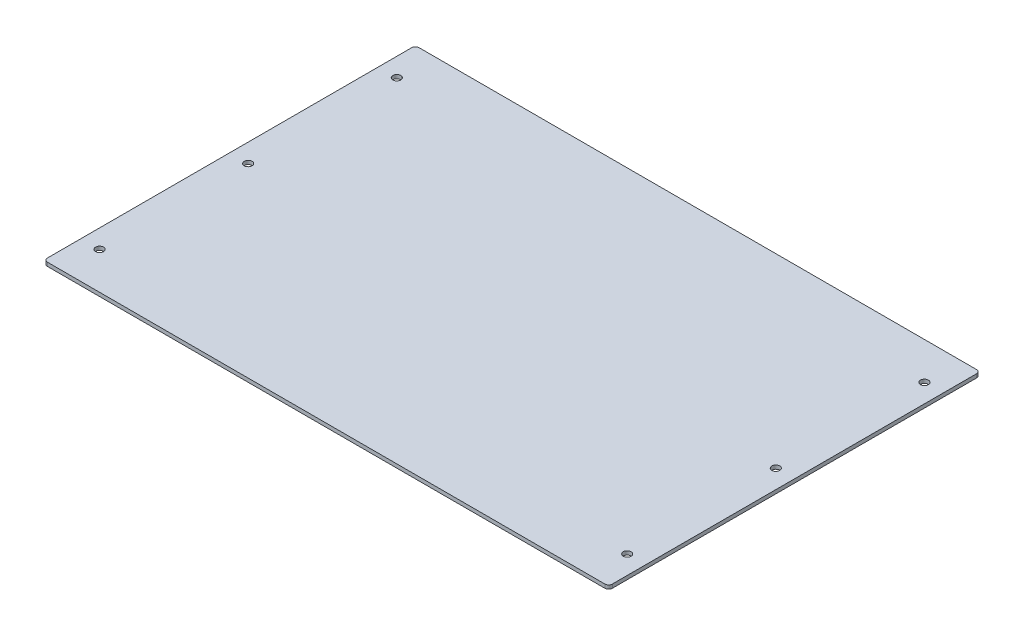
SolidWorks part; units mm, degrees
material "PC High Viscosity"
ref_plane "Front Plane" through (0, 0, 0) normal (0, 0, 1) x (1, 0, 0)
ref_plane "Top Plane" through (0, 0, 0) normal (0, 1, 0) x (1, 0, 0)
ref_plane "Right Plane" through (0, 0, 0) normal (1, 0, 0) x (0, 0, -1)
sketch "Sketch1" plane through (0, 0, 0) normal (0, 1, 0) x (1, 0, 0)
  line L1 (-238.125, -158.75) -> (238.125, -158.75)
  line L2 (-241.3, -155.575) -> (-241.3, 155.575)
  line L3 (-238.125, 158.75) -> (238.125, 158.75)
  line L4 (241.3, -155.575) -> (241.3, 155.575)
  line L5 (-241.3, -158.75) -> (241.3, 158.75) construction
  line L6 (-241.3, 158.75) -> (241.3, -158.75) construction
  arc A0 (-238.125, -158.75) -> (-241.3, -155.575) centre (-238.125, -155.575) cw
  arc A1 (238.125, -158.75) -> (241.3, -155.575) centre (238.125, -155.575) ccw
  arc A2 (238.125, 158.75) -> (241.3, 155.575) centre (238.125, 155.575) cw
  arc A3 (-241.3, 155.575) -> (-238.125, 158.75) centre (-238.125, 155.575) cw
  point P0 (0, 0)
  dimension "D3" = 3.175
  dimension "D1" = 482.6
  dimension "D2" = 317.5
extrude "Boss-Extrude1" add sketch "Sketch1" along normal blind 3.175
sketch "Sketch2" plane through (0, 3.175, 0) normal (0, 1, 0) x (1, 0, 0)
  line L0 (-225.425, -127) -> (-225.425, 127) construction
  line L1 (225.425, -127) -> (225.425, 127) construction
  line L2 (-241.3, 155.575) -> (-241.3, -155.575) construction
  line L3 (241.3, -155.575) -> (241.3, 155.575) construction
  point P3 (-225.425, 0)
  point P6 (225.425, 0)
  dimension "D2" = 254
  dimension "D3" = 15.875
  dimension "D4" = 15.875
hole_wizard "17/64 (0.26563) Diameter Hole1" positions "Sketch3" profile "Sketch4" hole size "17/64" standard "ANSI Inch" end condition through all
sketch "Sketch3" plane through (0, 3.175, 0) normal (0, 1, 0) x (1, 0, 0)
  point P0 (-225.425, 127)
  point P3 (-225.425, 0)
  point P6 (-225.425, -127)
  point P9 (225.425, 127)
  point P12 (225.425, 0)
  point P15 (225.425, -127)
sketch "Sketch4" plane through (-225.425, 3.175, -127) normal (1, 0, 0) x (0, 0, 1)
  line L0 (0, 0) -> (0, 3.175)
  line L1 (0, 3.175) -> (3.3735, 3.175)
  line L2 (3.3735, 3.175) -> (3.3735, 0)
  line L5 (3.3735, 0) -> (0, 0)
  line L11 (0, -6.35) -> (0, 107.95) construction
  dimension "Thru Hole Dia." = 6.747
  dimension "Thru Hole Depth" = 3.175
